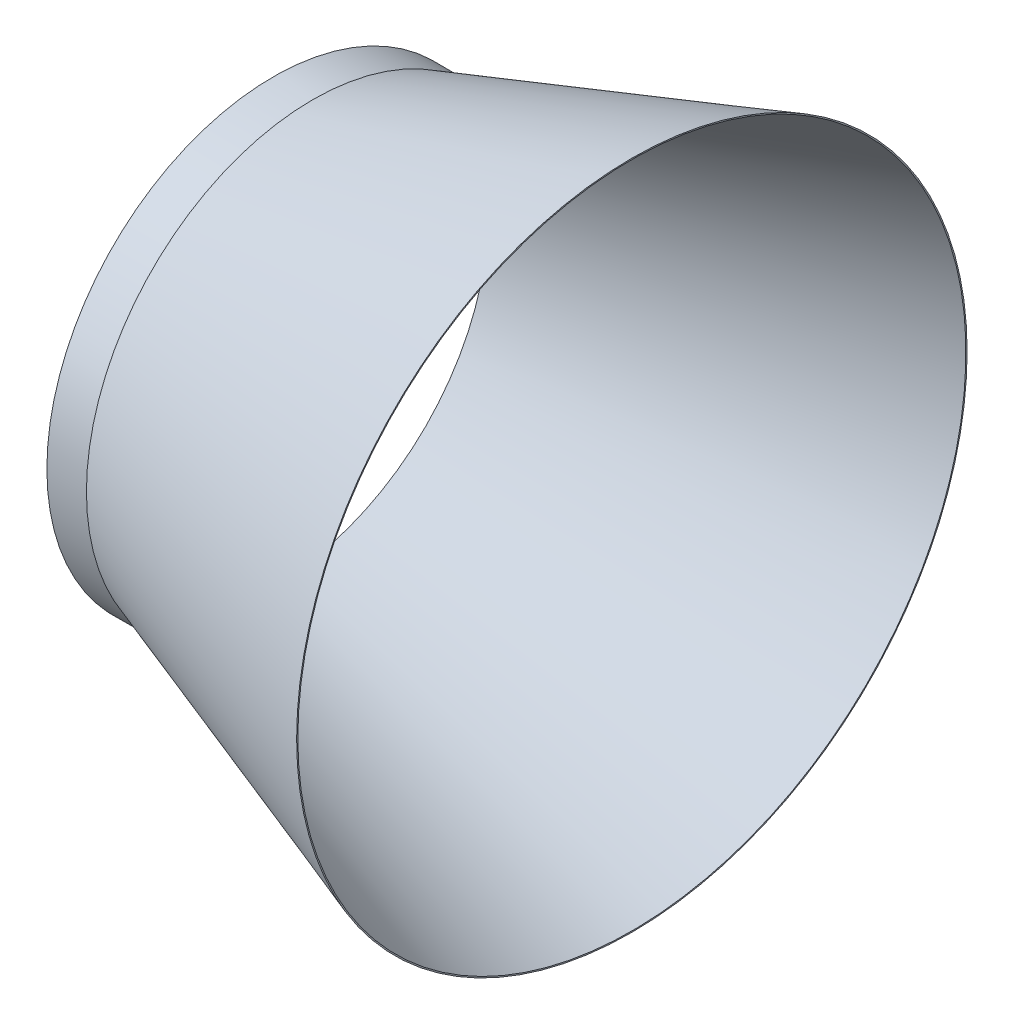
SolidWorks part; units mm, degrees
material "Tungsten"
ref_plane "Front Plane" through (0, 0, 0) normal (0, 0, 1) x (1, 0, 0)
ref_plane "Top Plane" through (0, 0, 0) normal (0, 1, 0) x (1, 0, 0)
ref_plane "Right Plane" through (0, 0, 0) normal (1, 0, 0) x (0, 0, -1)
sketch "Sketch1" plane through (0, 0, 0) normal (0, 0, 1) x (1, 0, 0)
  line L0 (0, 0) -> (0, 47.6758) construction
  line L1 (0, 0) -> (79.9592, 0) construction
  line L2 (79.9592, 0) -> (79.9592, 74.9554) construction
  line L3 (0, 47.6758) -> (45.8899, 47.6758) construction
  line L4 (0, 47.6758) -> (62.4191, 65.9935) construction
  line L5 (79.9592, 74.9554) -> (173.3924, 74.9554) construction
  line L6 (79.9592, 74.9554) -> (185.7919, 93.6166) construction
  line L10 (0, 47.6758) -> (79.9592, 74.9554)
  line L11 (0, 47.9442) -> (79.9592, 75.2238)
  line L12 (79.9592, 74.9554) -> (79.9592, 75.2238)
  line L13 (0, 47.6758) -> (0, 47.9442)
  line L14 (-0.082, 47.9162) -> (79.8772, 75.1958) construction
  dimension "D1" = 79.9592
  dimension "D2" = 47.6758
  dimension "D3" = 74.9554
  dimension "D4" = 16.355
  dimension "D5" = 10
  dimension "D6" = 0.254
revolve "Revolve1" add sketch "Sketch1" angle 360 about L1
sketch "Sketch3" plane through (0, 0, 0) normal (0, 0, 1) x (1, 0, 0)
  line L0 (79.9592, 75.2238) -> (0, 47.9442) construction
  line L1 (0, 47.9442) -> (8.3707, 50.8)
  line L3 (8.3707, 50.8) -> (-0.5036, 50.8)
  line L4 (-0.5036, 50.8) -> (0, 47.9442)
  line L5 (0, 0) -> (50000, 0) construction
  line L6 (0, 47.9442) -> (0, -47.9442) construction
  point P6 (8.3707, 50.8)
  point P12 (0, 0)
  point P13 (0, 0)
  point P14 (0, 0)
  point P15 (6.35, 50.8)
  point P16 (8.3306, 50.8)
  point P17 (6.35, 50.7863)
  point P18 (8.5188, 50.7863)
  dimension "D1" = 80
  dimension "D2" = 50.8
revolve "Revolve2" add sketch "Sketch3" angle 360 about L5
sketch "Sketch4" plane through (0, 0, 0) normal (-1, 0, 0) x (0, 0, 1)
  circle A0 centre (0, 67.31) radius 3.175
  circle A1 centre (20.7999, 64.0156) radius 3.175
  circle A2 centre (39.5638, 54.4549) radius 3.175
  circle A3 centre (54.4549, 39.5638) radius 3.175
  circle A4 centre (64.0156, 20.7999) radius 3.175
  circle A5 centre (67.31, 0) radius 3.175
  circle A6 centre (64.0156, -20.7999) radius 3.175
  circle A7 centre (54.4549, -39.5638) radius 3.175
  circle A8 centre (39.5638, -54.4549) radius 3.175
  circle A9 centre (20.7999, -64.0156) radius 3.175
  circle A10 centre (0, -67.31) radius 3.175
  circle A11 centre (-20.7999, -64.0156) radius 3.175
  circle A12 centre (-39.5638, -54.4549) radius 3.175
  circle A13 centre (-54.4549, -39.5638) radius 3.175
  circle A14 centre (-64.0156, -20.7999) radius 3.175
  circle A15 centre (-67.31, 0) radius 3.175
  circle A16 centre (-64.0156, 20.7999) radius 3.175
  circle A17 centre (-54.4549, 39.5638) radius 3.175
  circle A18 centre (-39.5638, 54.4549) radius 3.175
  circle A19 centre (-20.7999, 64.0156) radius 3.175
  point P44 (0, 0)
  dimension "D2" = 6.35
  dimension "D1" = 67.31
  dimension "D3" = 20
extrude "Cut-Extrude1" [suppressed] cut sketch "Sketch4" against normal up to next
